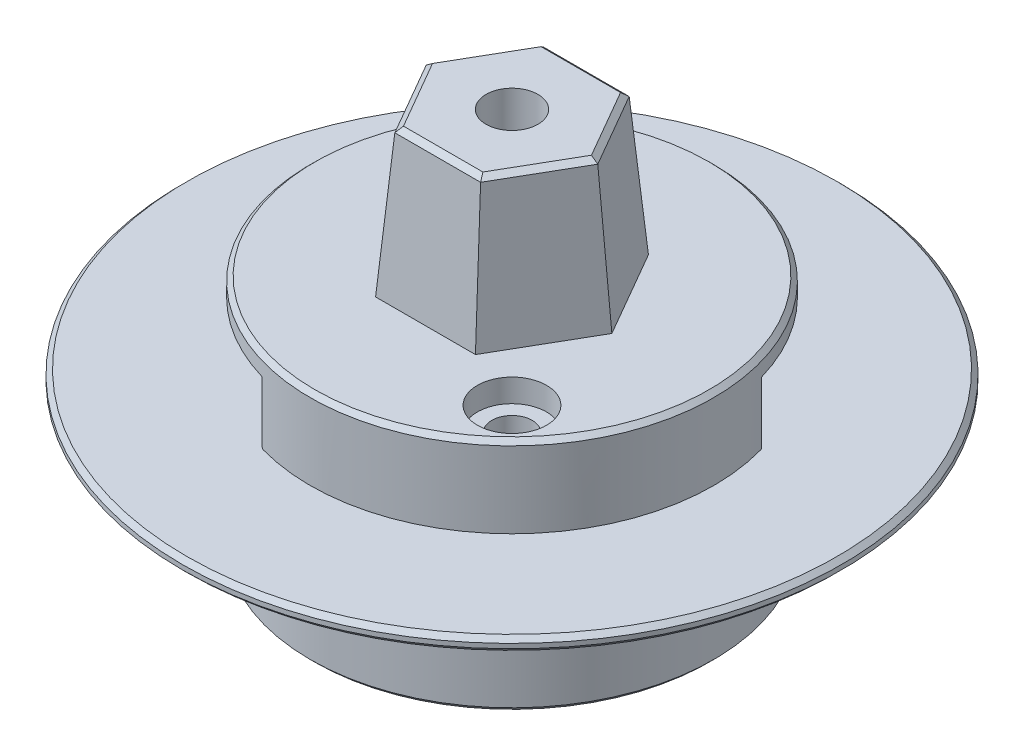
SolidWorks part; units mm, degrees
material "ABS"
ref_plane "Front Plane" through (0, 0, 0) normal (0, 0, 1) x (1, 0, 0)
ref_plane "Top Plane" through (0, 0, 0) normal (0, 1, 0) x (1, 0, 0)
ref_plane "Right Plane" through (0, 0, 0) normal (1, 0, 0) x (0, 0, -1)
sketch "Sketch1" plane through (0, 0, 0) normal (0, 1, 0) x (1, 0, 0)
  circle A0 centre (0, 0) radius 17.5
  circle A1 centre (0, 0) radius 7.5 construction
  circle A2 centre (7.5, 0) radius 1.75
  circle A3 centre (0, 7.5) radius 1.75
  circle A4 centre (-7.5, 0) radius 1.75
  circle A5 centre (0, -7.5) radius 1.75
  dimension "D1" = 3.5
  dimension "D2" = 15
  dimension "D3" = 35
extrude "Main Boss" add sketch "Sketch1" along normal blind 5.287
sketch "Sketch3" plane through (0, 5.287, 0) normal (0, 1, 0) x (1, 0, 0)
  circle A0 centre (0, 0) radius 14.8987
  circle A2 centre (-7.5, 0) radius 1.75 construction
  circle A3 centre (0, -7.5) radius 1.75 construction
  circle A4 centre (7.5, 0) radius 1.75 construction
  circle A5 centre (0, 7.5) radius 1.75 construction
  circle A6 centre (-7.5, 0) radius 1.75
  circle A7 centre (0, -7.5) radius 1.75
  circle A8 centre (7.5, 0) radius 1.75
  circle A9 centre (0, 7.5) radius 1.75
  dimension "D1" = 29.7974
extrude "Codewheel Center Boss" add sketch "Sketch3" along normal blind 0.5
sketch "Sketch4" plane through (0, 5.287, 0) normal (0, 1, 0) x (1, 0, 0)
  circle A0 centre (0, 0) radius 16.5
  circle A1 centre (0, 0) radius 17.5 construction
  circle A2 centre (0, 0) radius 14.8987 construction
  circle A3 centre (0, 0) radius 14.8987
  dimension "D1" = 1
extrude "Codewheel Relief Cut" cut sketch "Sketch4" against normal blind 0.4
chamfer "Codewheel Relief Chamfer" distance 0.4 angle 45 1 edges at (0, 4.887, 16.5)
ref_plane "Plane1" through (0, 5.4648, 0) normal (0, 1, 0) x (1, 0, 0)
sketch "Sketch6" plane through (0, 5.4648, 0) normal (0, 1, 0) x (1, 0, 0)
  circle A0 centre (0, 0) radius 16.5 construction
  circle A1 centre (0, 0) radius 17.5 construction
  circle A2 centre (0, 0) radius 16.5
  circle A3 centre (0, 0) radius 17.5
extrude "Codewheel Top Boss" add sketch "Sketch6" along normal blind 1 separate body
sketch "Sketch7" plane through (0, 6.4648, 0) normal (0, 1, 0) x (1, 0, 0)
  circle A0 centre (0, 0) radius 17.5 construction
  circle A1 centre (0, 0) radius 17.5
  circle A2 centre (0, -7.5) radius 1.75 construction
  circle A3 centre (7.5, 0) radius 1.75 construction
  circle A4 centre (-7.5, 0) radius 1.75 construction
  circle A5 centre (0, 7.5) radius 1.75 construction
  circle A6 centre (0, -7.5) radius 1.75
  circle A7 centre (7.5, 0) radius 1.75
  circle A8 centre (-7.5, 0) radius 1.75
  circle A9 centre (0, 7.5) radius 1.75
extrude "Secondary Boss" add sketch "Sketch7" along normal blind 7
chamfer "Codewheel Relief Chamfer 2" distance 1 angle 45 1 edges at (0, 6.4648, 16.5)
sketch "Sketch8" plane through (0, 13.4648, 0) normal (0, 1, 0) x (1, 0, 0)
  circle A0 centre (-7.5, 0) radius 3
  circle A1 centre (0, 7.5) radius 3
  circle A2 centre (7.5, 0) radius 3
  circle A3 centre (0, -7.5) radius 3
  dimension "D1" = 6
extrude "Motor Bolt Countersinks" cut sketch "Sketch8" against normal blind 5
chamfer "Edge Chamfers 1" distance 0.4 angle 45 2 edges at (0, 0, 17.5) (0, 5.287, 17.5)
chamfer "Edge Chamfers 2" distance 0.4 angle 45 2 edges at (0, 13.4648, 17.5) (0, 5.4648, 17.5)
sketch "Sketch11" plane through (0, 13.4648, 0) normal (0, 1, 0) x (1, 0, 0)
  line L0 (0, 0) -> (20.32, 0) construction
  line L9 (-16.1645, -1.7961) -> (1.7961, 16.1645)
  line L10 (-16.1645, -1.7961) -> (-1.7961, -16.1645)
  line L11 (1.7961, 16.1645) -> (16.1645, 1.7961)
  line L12 (-1.7961, -16.1645) -> (16.1645, 1.7961)
  line L13 (-16.1645, -1.7961) -> (16.1645, 1.7961) construction
  dimension "D1" = 25.4
  dimension "D2" = 20.32
  dimension "D3" = 45
extrude "Accelerometer Notch" cut sketch "Sketch11" against normal blind 2
sketch "Sketch13" plane through (0, 13.4648, 0) normal (0, 1, 0) x (1, 0, 0)
  line L0 (-9.7227, 9.7227) -> (9.7227, -9.7227) construction
  line L1 (9.7227, -9.7227) -> (9.7227, 9.7227) construction
  line L2 (9.7227, 9.7227) -> (-9.7227, -9.7227) construction
  line L3 (-9.7227, -9.7227) -> (9.7227, -9.7227) construction
  circle A0 centre (0, 0) radius 13.75 construction
  circle A1 centre (9.7227, 9.7227) radius 2.35 construction
  circle A2 centre (-9.7227, 9.7227) radius 2.35
  circle A3 centre (-9.7227, -9.7227) radius 2.35 construction
  circle A4 centre (9.7227, -9.7227) radius 2.35
  dimension "D1" = 27.5
  dimension "D2" = 4.7
extrude "Accelerometer Layer Heat Set Insert Holes" cut sketch "Sketch13" against normal blind 4.2
sketch "Sketch14" plane through (0, 9.2648, 0) normal (0, 1, 0) x (1, 0, 0)
  circle A0 centre (-9.7227, 9.7227) radius 1.75
  circle A1 centre (9.7227, -9.7227) radius 1.75
  dimension "D1" = 3.5
extrude "Accelerometer Layer Bolt Through Holes" cut sketch "Sketch14" against normal blind 2
sketch "Sketch15" plane through (0, 13.4648, 0) normal (0, 1, 0) x (1, 0, 0)
  line L5 (-16.7168, -5.1768) -> (5.1768, 16.7168)
  line L6 (1.7961, 16.1645) -> (-16.1645, -1.7961) construction
  line L7 (-5.1768, -16.7168) -> (16.7168, 5.1768)
  arc A0 (5.1768, 16.7168) -> (-16.7168, -5.1768) centre (0, 0) ccw
  circle A1 centre (0, 0) radius 17.5 construction
  circle A3 centre (9.7227, -9.7227) radius 1.75
  circle A5 centre (-9.7227, 9.7227) radius 1.75 construction
  circle A9 centre (-9.7227, 9.7227) radius 1.75
  circle A13 centre (9.7227, -9.7227) radius 2.35 construction
  arc A14 (-5.1768, -16.7168) -> (16.7168, 5.1768) centre (0, 0) ccw
  dimension "D1" = 2
extrude "Accelerometer Cover" add sketch "Sketch15" along normal blind 5 separate body
sketch "Sketch17" plane through (0, 18.4648, 0) normal (0, 1, 0) x (1, 0, 0)
  circle A0 centre (0, 0) radius 17.5
  arc A1 (5.1768, 16.7168) -> (-16.7168, -5.1768) centre (0, 0) ccw construction
  circle A3 centre (-9.7227, 9.7227) radius 1.75 construction
  circle A5 centre (9.7227, -9.7227) radius 1.75
  circle A7 centre (-9.7227, 9.7227) radius 1.75
  circle A11 centre (9.7227, -9.7227) radius 1.75 construction
extrude "Accelerometer Cover Boss" add sketch "Sketch17" along normal blind 2
sketch "Sketch19" plane through (0, 20.4648, 0) normal (0, 1, 0) x (1, 0, 0)
  circle A0 centre (-9.7227, 9.7227) radius 3
  circle A4 centre (9.7227, -9.7227) radius 3
  dimension "D1" = 6
extrude "Acclerometer Cover Countersinks" cut sketch "Sketch19" against normal blind 2
chamfer "Edge Chamfers 3" distance 0.4 angle 45 2 edges at (0, 20.4648, 17.5) (-12.3744, 13.4648, -12.3744)
sketch "Sketch18" plane through (0, 20.4648, 0) normal (0, 1, 0) x (1, 0, 0)
  line L1 (4.3301, 7.5) -> (-4.3301, 7.5)
  line L2 (-4.3301, 7.5) -> (-8.6603, 0)
  line L3 (-8.6603, 0) -> (-4.3301, -7.5)
  line L4 (-4.3301, -7.5) -> (4.3301, -7.5)
  line L5 (4.3301, -7.5) -> (8.6603, 0)
  line L6 (8.6603, 0) -> (4.3301, 7.5)
  circle A0 centre (0, 0) radius 7.5 construction
  dimension "D1" = 15
extrude "Output Cone" add sketch "Sketch18" along normal blind 12.5 draft 5
chamfer "Chamfer1" distance 0.4 angle 45 6 edges at (5.5481, 32.9648, 3.2032) (0, 32.9648, 6.4064) (-5.5481, 32.9648, 3.2032) (-5.5481, 32.9648, -3.2032) (0, 32.9648, -6.4064) (5.5481, 32.9648, -3.2032)
sketch "Sketch20" plane through (0, 32.9648, 0) normal (0, 1, 0) x (1, 0, 0)
  circle A0 centre (0, 0) radius 2.25
  dimension "D1" = 4.5
extrude "Cut-Extrude1" cut sketch "Sketch20" against normal blind 10
sketch "Sketch21" plane through (0, 11.4648, 0) normal (0, 1, 0) x (1, 0, 0)
  line L0 (-1.7961, -12.5724) -> (-12.5724, -1.7961) construction
  line L1 (-1.7961, -12.5724) -> (12.5724, 1.7961) construction
  line L2 (-12.5724, -1.7961) -> (1.7961, 12.5724) construction
  line L3 (12.5724, 1.7961) -> (1.7961, 12.5724) construction
  line L4 (-1.7961, -12.5724) -> (1.7961, 12.5724) construction
  line L5 (-12.5724, -1.7961) -> (12.5724, 1.7961) construction
  line L6 (1.7961, 16.1645) -> (-16.1645, -1.7961) construction
  circle A0 centre (1.7961, 12.5724) radius 0.8
  circle A1 centre (-12.5724, -1.7961) radius 0.8
  circle A2 centre (-1.7961, -12.5724) radius 0.8
  circle A3 centre (12.5724, 1.7961) radius 0.8
  point P1 (0, 0)
  dimension "D3" = 1.6
  dimension "D1" = 20.32
  dimension "D2" = 15.24
extrude "Cut-Extrude2" cut sketch "Sketch21" against normal blind 5
sketch "Sketch22" plane through (0, 13.4648, 0) normal (0, 1, 0) x (1, 0, 0)
  line L8 (-1.7961, -16.518) -> (16.518, 1.7961)
  line L9 (-16.518, -1.7961) -> (-1.7961, -16.518)
  line L10 (1.7961, 16.518) -> (-16.518, -1.7961)
  line L11 (16.518, 1.7961) -> (1.7961, 16.518)
  line L12 (-1.7961, -16.518) -> (16.518, 1.7961)
  line L13 (-16.518, -1.7961) -> (-1.7961, -16.518)
  line L14 (1.7961, 16.518) -> (-16.518, -1.7961)
  line L15 (16.518, 1.7961) -> (1.7961, 16.518)
  dimension "D1" = 0.25
extrude "Cut-Extrude3" cut sketch "Sketch22" against normal up to surface (2 mm away) up to face at (1.7961, 11.4648, -11.7724)
sketch "Sketch23" plane through (0, 13.4648, 0) normal (0, 1, 0) x (1, 0, 0)
  circle A0 centre (0, 0) radius 28.575
  circle A1 centre (0, 0) radius 17.1
  circle A2 centre (0, 0) radius 17.1 construction
  dimension "D1" = 57.15
extrude "Boss-Extrude1" add sketch "Sketch23" against normal blind 1.2
chamfer "Chamfer2" distance 0.4 angle 45 6 edges at (0, 13.4648, 28.575) (0, 12.2648, 28.575) (7.361, 13.4648, 7.361) (-9.157, 13.4648, 9.157) (-7.361, 13.4648, -7.361) (9.157, 13.4648, -9.157)
chamfer "Chamfer3" distance 0.4 angle 45 8 edges at (-12.3744, 18.4648, 12.3744) (12.3744, 18.4648, -12.3744) (-5.1768, 15.9648, 16.7168) (16.7168, 15.9648, -5.1768) (5.77, 13.4648, 5.77) (5.1768, 16.1648, -16.7168) (-16.7168, 16.1648, 5.1768) (-5.77, 13.4648, -5.77)
